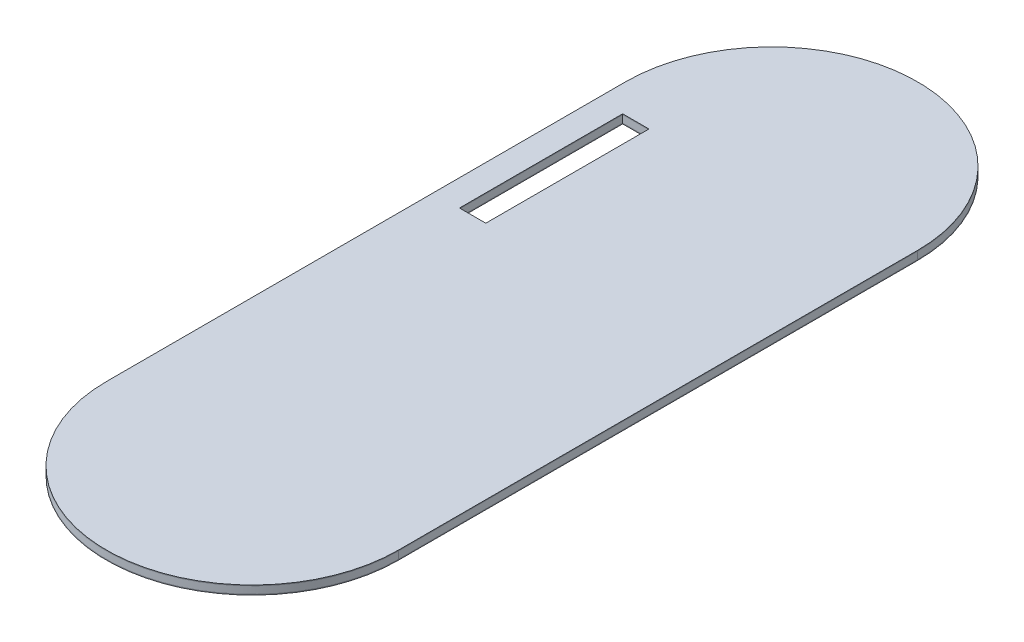
SolidWorks part; units mm, degrees
ref_plane "Front Plane" through (0, 0, 0) normal (0, 0, 1) x (1, 0, 0)
ref_plane "Top Plane" through (0, 0, 0) normal (0, 1, 0) x (1, 0, 0)
ref_plane "Right Plane" through (0, 0, 0) normal (1, 0, 0) x (0, 0, -1)
sketch "Sketch1" plane through (0, 0, 0) normal (0, 1, 0) x (1, 0, 0)
  line L0 (0, -88.9) -> (0, 88.9) construction
  line L2 (50, 88.9) -> (50, -88.9)
  line L8 (-41, 23.02) -> (-41, 78.9)
  line L11 (-41, 78.9) -> (-32, 78.9)
  line L12 (-32, 78.9) -> (-32, 23.02)
  line L13 (-32, 23.02) -> (-41, 23.02)
  line L14 (-50, 88.9) -> (-50, -88.9)
  arc A0 (50, 88.9) -> (-50, 88.9) centre (0, 88.9) ccw
  arc A1 (-50, -88.9) -> (50, -88.9) centre (0, -88.9) ccw
  point P8 (0, 0)
  point P13 (-89.4761, 0)
  point P18 (-41, 50.96)
  dimension "D2" = 100
  dimension "D1" = 177.8
  dimension "D3" = 55.88
  dimension "D4" = 9
  dimension "D5" = 10
  dimension "D6" = 9
extrude "Boss-Extrude1" add sketch "Sketch1" along normal blind 0.25
sketch "Sketch2" plane through (0, 0.25, 0) normal (0, 1, 0) x (1, 0, 0)
  line L0 (-32, 78.9) -> (-41, 78.9) construction
  line L1 (-41, 78.9) -> (-41, 23.02) construction
  line L2 (-50, 88.9) -> (-50, -88.9)
  line L3 (50, -88.9) -> (50, 88.9)
  line L4 (-50, 88.9) -> (-50, -88.9)
  line L5 (50, -88.9) -> (50, 88.9)
  line L6 (-41, 23.02) -> (-32, 23.02) construction
  line L7 (-32, 23.02) -> (-32, 78.9) construction
  line L8 (-32, 78.9) -> (-41, 78.9)
  line L9 (-41, 78.9) -> (-41, 23.02)
  line L10 (-41, 23.02) -> (-32, 23.02)
  line L11 (-32, 23.02) -> (-32, 78.9)
  arc A2 (50, 88.9) -> (-50, 88.9) centre (0, 88.9) ccw
  arc A3 (-50, -88.9) -> (50, -88.9) centre (0, -88.9) ccw
  arc A4 (50, 88.9) -> (-50, 88.9) centre (0, 88.9) ccw
  arc A5 (-50, -88.9) -> (50, -88.9) centre (0, -88.9) ccw
  arc M5 (50, 88.9) -> (-50, 88.9) centre (0, 88.9) ccw
  line M6 (-50, 88.9) -> (-50, -88.9)
  arc M7 (-50, -88.9) -> (50, -88.9) centre (0, -88.9) ccw
  line M8 (50, -88.9) -> (50, 88.9)
  line M9 (-41, 78.9) -> (-32, 78.9)
  line M10 (-32, 78.9) -> (-32, 23.02)
  line M11 (-32, 23.02) -> (-41, 23.02)
  line M12 (-41, 23.02) -> (-41, 78.9)
  dimension "D1" = 0
extrude "Boss-Extrude3" add sketch "Sketch2" along normal blind 2.5 separate body contours M8 M5 M6 M7 M12 M9 M10 M11 region at (0.7304, 0.25, 1.0198)
sketch "Sketch3" plane through (0, 2.75, 0) normal (0, 1, 0) x (1, 0, 0)
  line L4 (-41, 78.9) -> (-41, 23.02)
  line L5 (-32, 78.9) -> (-41, 78.9)
  line L6 (-32, 23.02) -> (-32, 78.9)
  line L7 (-41, 23.02) -> (-32, 23.02)
  line L8 (-41, 78.9) -> (-41, 23.02)
  line L9 (-32, 78.9) -> (-41, 78.9)
  line L10 (-32, 23.02) -> (-32, 78.9)
  line L11 (-41, 23.02) -> (-32, 23.02)
  line M5 (-41, 23.02) -> (-41, 78.9)
  line M6 (-41, 78.9) -> (-32, 78.9)
  line M7 (-32, 78.9) -> (-32, 23.02)
  line M8 (-32, 23.02) -> (-41, 23.02)
  line M9 (50, -88.9) -> (50, 88.9)
  arc M10 (50, 88.9) -> (-50, 88.9) centre (0, 88.9) ccw
  line M11 (-50, 88.9) -> (-50, -88.9)
  arc M12 (-50, -88.9) -> (50, -88.9) centre (0, -88.9) ccw
  dimension "D1" = 0
extrude "Boss-Extrude4" add sketch "Sketch3" along normal blind 0.25 separate body contours M12 M9 M10 M11 M8 M5 M6 M7 region at (0.7304, 2.75, 1.0198)
